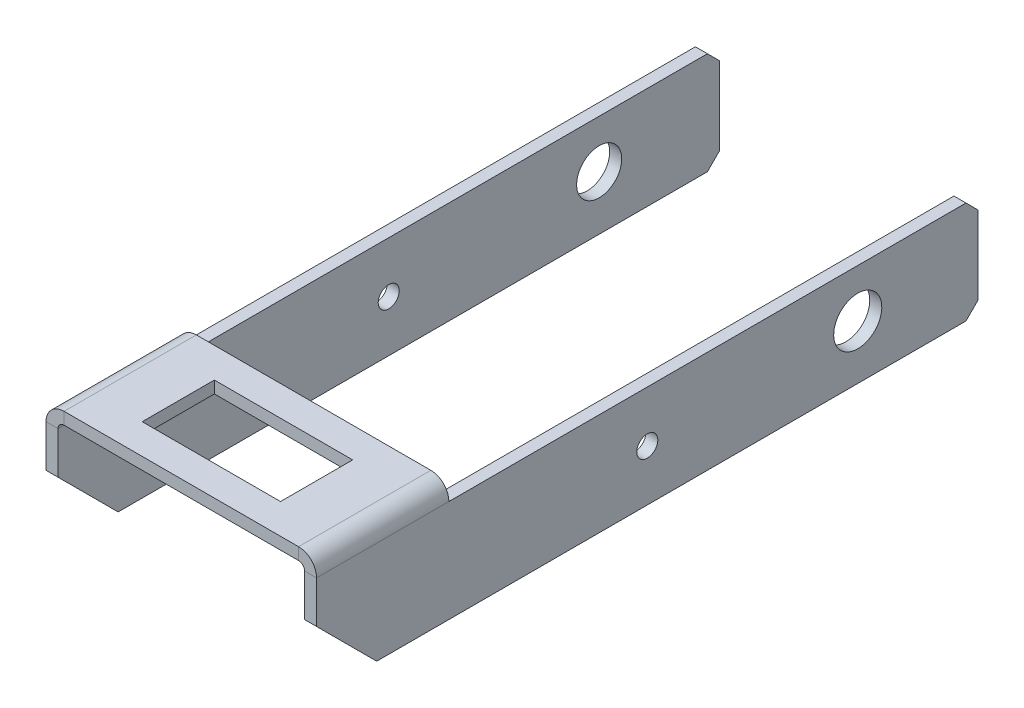
SolidWorks part; units mm, degrees
note: The reader was unsure of these and kept them because the rebuilt part matched: flange length of "Edge-Flange3".
ref_plane "Front Plane" through (0, 0, 0) normal (0, 0, 1) x (1, 0, 0)
ref_plane "Top Plane" through (0, 0, 0) normal (0, 1, 0) x (1, 0, 0)
ref_plane "Right Plane" through (0, 0, 0) normal (1, 0, 0) x (0, 0, -1)
sketch "Sketch1" plane through (0, 0, 0) normal (0, 1, 0) x (1, 0, 0)
  line L1 (0, 0) -> (45, 0)
  line L2 (0, 0) -> (0, 22)
  line L3 (0, 22) -> (45, 22)
  line L4 (45, 0) -> (45, 22)
  dimension "D1" = 22
  dimension "D2" = 45
base flange "Base-Flange1" sketch "Sketch1" thickness 2 reverse thickness direction yes parameters "D1"=1
edge flange "Edge-Flange3" sketch "Sketch32" flange profiles "Sketch32", "Sketch33" flange angle 90 flange length 20 flange position material inside bend radius 1 thickness 2 relief rectangular parameters "D6"=10, "D8"=1
sketch "Sketch32" plane through (45, 0, 0) normal (1, 0, 0) x (0, 0, 1)
  line L0 (0, 0) -> (-22, 0) construction
  line L1 (0, 0) -> (-110, 0)
  line L2 (-110, 0) -> (-110, 18)
  line L3 (-110, 18) -> (0, 18)
  line L4 (0, 18) -> (0, 0)
  dimension "D1" = 110
sketch "Sketch33" plane through (0, 0, 0) normal (-1, 0, 0) x (0, 0, -1)
  line L0 (22, 0) -> (0, 0) construction
  line L1 (110, 0) -> (0, 0)
  line L2 (0, 0) -> (0, 18)
  line L3 (0, 18) -> (110, 18)
  line L4 (110, 18) -> (110, 0)
  dimension "D1" = 110
bend "EdgeBend5" bend radius 1 bend angle 90 parameters "D5"=1
bend "EdgeBend6" bend radius 1 bend angle 90 parameters "D5"=2
sketch "Sketch34" plane through (45, 0, 0) normal (1, 0, 0) x (0, 0, -1)
  line L0 (110, -9) -> (90, -9) construction
  line L1 (110, 0) -> (110, -18) construction
  line L2 (0, -1) -> (0, -18) construction
  circle A0 centre (90, -9) radius 4
  dimension "D1" = 8
  dimension "D2" = 90
extrude "Cut-Extrude1" cut sketch "Sketch34" against normal blind 10 normal cut yes
sketch "Sketch35" plane through (0, 0, 0) normal (-1, 0, 0) x (0, 0, 1)
  line L0 (-110, -9) -> (-90, -9) construction
  line L1 (-110, 0) -> (-110, -18) construction
  line L2 (0, -18) -> (0, -1) construction
  circle A0 centre (-90, -9) radius 3.75
  dimension "D1" = 7.5
  dimension "D2" = 90
extrude "Cut-Extrude2" cut sketch "Sketch35" against normal blind 10 normal cut yes
sketch "Sketch36" plane through (0, 0, 0) normal (-1, 0, 0) x (0, 0, 1)
  line L0 (-110, -9.5) -> (-55, -9.5) construction
  line L1 (-110, -1) -> (-110, -18) construction
  circle A0 centre (-55, -9.5) radius 1.75
  dimension "D2" = 3.5
  dimension "D1" = 55
extrude "Cut-Extrude3" cut sketch "Sketch36" against normal through all normal cut yes
sketch "Sketch37" plane through (0, 2, 0) normal (0, 1, 0) x (1, 0, 0)
  line L0 (22.5, 22) -> (22.5, 0) construction
  line L1 (42, 22) -> (3, 22) construction
  line L2 (3, 0) -> (42, 0) construction
  line L4 (11, 5) -> (34, 5)
  line L5 (11, 5) -> (11, 17)
  line L6 (11, 17) -> (34, 17)
  line L7 (34, 5) -> (34, 17)
  line L8 (11, 5) -> (34, 17) construction
  line L9 (11, 17) -> (34, 5) construction
  point P6 (22.5, 11)
  dimension "D1" = 23
  dimension "D2" = 12
extrude "Cut-Extrude4" cut sketch "Sketch37" against normal blind 10 normal cut yes
chamfer "Chamfer1" distance 2 angle 45 4 edges at (1, -1, -110) (1, -18, -110) (44, -18, -110) (44, -1, -110)
chamfer "Chamfer2" distance 10 angle 45 2 edges at (44, -18, 0) (1, -18, 0)
sketch "Bend-Lines1" [suppressed] plane through (0, 0, 0) normal (0, 1, 0) x (1, 0, 0)
sketch "Bounding-Box1" [suppressed] plane through (0, 0, 0) normal (0, 1, 0) x (1, 0, 0)
sheet metal parameters "Sheet-Metal1" thickness 2 parameters "D1"=1
flat pattern "Flat-Pattern1" [suppressed]
sketch "Bend-Lines2" plane through (0, 0, 0) normal (0, 1, 0) x (1, 0, 0)
sketch3d "Bounding-Box2" [suppressed]
  line L0 (-40, 22, 0) -> (0, 22, 0) construction
  line L1 (-40, 0, 0) -> (0, 0, 0) construction
  line L2 (-40, 22, 0) -> (-40, 0, 0) construction
  line L3 (0, 22, 0) -> (0, 0, 0) construction
sheet metal parameters "Sheet-Metal4" thickness 2 parameters "D1"=1
flat pattern "Flat-Pattern1"
sketch "Bend-Lines2" plane through (0, 0, 0) normal (0, -1, 0) x (-1, 0, 0)
  line L0 (-1.4292, 0) -> (-1.4292, 22) construction
  line L1 (-38.5708, 22) -> (-38.5708, 0) construction
  line L2 (-1.4292, 0) -> (-1.4292, 22) construction
  line L3 (-38.5708, 22) -> (-38.5708, 0) construction
sketch3d "Bounding-Box2" [suppressed]
  line L0 (17.1416, 0, 0) -> (17.1416, 110, 0) construction
  line L1 (-57.1416, 0, 0) -> (-57.1416, 110, 0) construction
  line L2 (17.1416, 0, 0) -> (-57.1416, 0, 0) construction
  line L3 (17.1416, 110, 0) -> (-57.1416, 110, 0) construction
bend of the flat pattern "Flatten-<EdgeBend5>1"
bend of the flat pattern "Flatten-<EdgeBend6>1"
sheet metal parameters "Sheet-Metal5" thickness 2 parameters "D1"=1
flat pattern "Flat-Pattern1"
sketch "Bend-Lines2" plane through (0, 0, 0) normal (0, -1, 0) x (-1, 0, 0)
  line L0 (-1.4292, 0) -> (-1.4292, 22) construction
  line L1 (-38.5708, 22) -> (-38.5708, 0) construction
  line L2 (-1.4292, 0) -> (-1.4292, 22) construction
  line L3 (-38.5708, 22) -> (-38.5708, 0) construction
sketch3d "Bounding-Box2" [suppressed]
  line L0 (17.1416, 0, 0) -> (17.1416, 110, 0) construction
  line L1 (-57.1416, 0, 0) -> (-57.1416, 110, 0) construction
  line L2 (17.1416, 0, 0) -> (-57.1416, 0, 0) construction
  line L3 (17.1416, 110, 0) -> (-57.1416, 110, 0) construction
bend of the flat pattern "Flatten-<EdgeBend5>1"
bend of the flat pattern "Flatten-<EdgeBend6>1"
sheet metal parameters "Sheet-Metal6" thickness 2 parameters "D1"=1
flat pattern "Flat-Pattern1"
sketch "Bend-Lines2" plane through (0, 0, 0) normal (0, -1, 0) x (-1, 0, 0)
  line L0 (-1.4292, 0) -> (-1.4292, 22) construction
  line L1 (-38.5708, 22) -> (-38.5708, 0) construction
  line L2 (-1.4292, 0) -> (-1.4292, 22) construction
  line L3 (-38.5708, 22) -> (-38.5708, 0) construction
sketch3d "Bounding-Box2" [suppressed]
  line L0 (17.1416, 0, 0) -> (17.1416, 110, 0) construction
  line L1 (-57.1416, 0, 0) -> (-57.1416, 110, 0) construction
  line L2 (17.1416, 0, 0) -> (-57.1416, 0, 0) construction
  line L3 (17.1416, 110, 0) -> (-57.1416, 110, 0) construction
bend of the flat pattern "Flatten-<EdgeBend5>1"
bend of the flat pattern "Flatten-<EdgeBend6>1"
sheet metal parameters "Sheet-Metal7" thickness 2 parameters "D1"=1
flat pattern "Flat-Pattern1"
sketch "Bend-Lines2" plane through (0, 0, 0) normal (0, -1, 0) x (-1, 0, 0)
  line L0 (-1.4292, 0) -> (-1.4292, 22) construction
  line L1 (-38.5708, 22) -> (-38.5708, 0) construction
  line L2 (-1.4292, 0) -> (-1.4292, 22) construction
  line L3 (-38.5708, 22) -> (-38.5708, 0) construction
sketch3d "Bounding-Box2" [suppressed]
  line L0 (17.1416, 0, 0) -> (17.1416, 110, 0) construction
  line L1 (-57.1416, 0, 0) -> (-57.1416, 110, 0) construction
  line L2 (17.1416, 0, 0) -> (-57.1416, 0, 0) construction
  line L3 (17.1416, 110, 0) -> (-57.1416, 110, 0) construction
bend of the flat pattern "Flatten-<EdgeBend5>1"
bend of the flat pattern "Flatten-<EdgeBend6>1"
sheet metal parameters "Sheet-Metal8" thickness 2 parameters "D1"=1
flat pattern "Flat-Pattern1"
sketch "Bend-Lines2" plane through (0, 0, 0) normal (0, -1, 0) x (-1, 0, 0)
  line L0 (-1.4292, 0) -> (-1.4292, 22) construction
  line L1 (-43.5708, 22) -> (-43.5708, 0) construction
  line L2 (-1.4292, 0) -> (-1.4292, 22) construction
  line L3 (-43.5708, 22) -> (-43.5708, 0) construction
sketch3d "Bounding-Box2" [suppressed]
  line L0 (17.1416, 0, 0) -> (17.1416, 110, 0) construction
  line L1 (-62.1416, 0, 0) -> (-62.1416, 110, 0) construction
  line L2 (17.1416, 0, 0) -> (-62.1416, 0, 0) construction
  line L3 (17.1416, 110, 0) -> (-62.1416, 110, 0) construction
bend of the flat pattern "Flatten-<EdgeBend5>1"
bend of the flat pattern "Flatten-<EdgeBend6>1"
